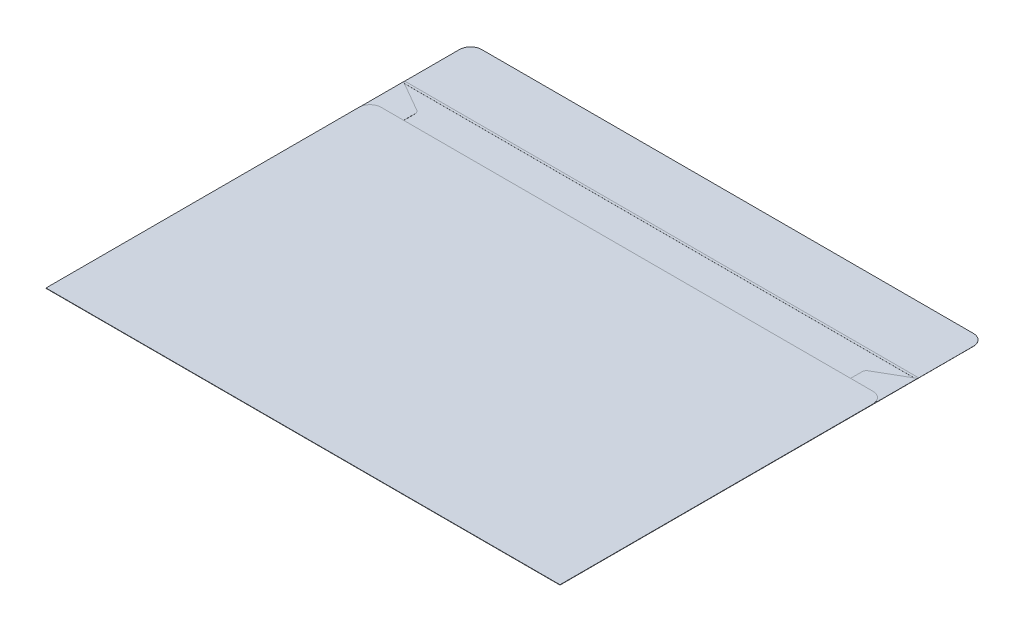
SolidWorks part; units mm, degrees
ref_plane "Front Plane" through (0, 0, 0) normal (0, 0, 1) x (1, 0, 0)
ref_plane "Top Plane" through (0, 0, 0) normal (0, 1, 0) x (1, 0, 0)
ref_plane "Right Plane" through (0, 0, 0) normal (1, 0, 0) x (0, 0, -1)
sketch "Sketch1" plane through (0, 0, 0) normal (0, 1, 0) x (1, 0, 0)
  line L2 (-115, 80) -> (-115, -80)
  line L3 (-115, -80) -> (115, -80)
  line L4 (115, 80) -> (115, -80)
  line L5 (0, -80) -> (0, 80) construction
  line L6 (-115, 0) -> (115, 0) construction
  line L8 (-115, 80) -> (-115, 105)
  line L9 (-110, 110) -> (110, 110)
  line L10 (115, 80) -> (115, 105)
  line L11 (0, 110) -> (0, 80) construction
  line L12 (-115, 92.5) -> (115, 92.5) construction
  arc A0 (110, 110) -> (115, 105) centre (110, 105) cw
  arc A1 (-110, 110) -> (-115, 105) centre (-110, 105) ccw
  point P0 (0, 0)
  point P11 (-115, 110)
  point P301 (0, 92.5)
  dimension "D4" = 5
  dimension "D1" = 160
  dimension "D2" = 230
  dimension "D3" = 30
extrude "Boss-Extrude1" add sketch "Sketch1" along normal blind 0.05
sketch "Sketch2" plane through (0, 0.05, 0) normal (0, 1, 0) x (1, 0, 0)
  line L0 (115, -80) -> (115, 105) construction
  line L1 (-115, -80) -> (115, -80)
  line L2 (-115, -80) -> (-115, 65)
  line L3 (-115, 65) -> (115, 65)
  line L4 (115, -80) -> (115, 65)
  line L5 (0, 65) -> (0, -80) construction
  line L6 (-115, -7.5) -> (115, -7.5) construction
  line L7 (-115, -80) -> (-115, 80)
  line L8 (-115, 105) -> (-115, -80) construction
  line L9 (-115, 80) -> (-100, 71.3397)
  line L10 (-100, 71.3397) -> (-100, -80)
  line L11 (-100, -80) -> (-115, -80)
  line L12 (100, -80) -> (115, -80)
  line L13 (100, 71.3397) -> (100, -80)
  line L14 (115, 80) -> (100, 71.3397)
  line L15 (115, -80) -> (115, 80)
  line L16 (-115, 80.5) -> (-115, 79.5) construction
  line L17 (-115, 80.5) -> (115, 80.5) construction
  line L18 (-115, 79.5) -> (115, 79.5) construction
  line L19 (115, 80.5) -> (115, 79.5) construction
  line L20 (-115, 80.5) -> (115, 79.5) construction
  line L21 (-115, 79.5) -> (115, 80.5) construction
  point P14 (0, 0)
  point P15 (0, 80)
  point P16 (0, 0)
  point P484 (0, -7.5)
  line M14 (115, -80) -> (115, 105)
  line M18 (-115, 105) -> (-115, -80)
  line M19 (-115, -80) -> (115, -80)
  dimension "D1" = 145
  dimension "D2" = 15
  dimension "D3" = 60
  dimension "D4" = 160
  dimension "D5" = 230
  dimension "D6" = 1
  dimension "D7" = 15
extrude "Boss-Extrude2" add sketch "Sketch2" along normal blind 0.1 contours L13 L3 L10 L1 | L10 L3 M18 M19 | L3 L13 M19 M14 region at (-107.5, 0.05, 7.5) region at (0, 0.05, 7.5) region at (107.5, 0.05, 7.5)
extrude "Boss-Extrude3" add sketch "Sketch2<3>" along normal blind 0.05 contours L18 L7 L3 L10 L9 | L18 L14 L13 L3 M14 region at (-108.5146, 0.05, -70.6278) region at (108.5146, 0.05, -70.6278)
sketch "Sketch2<3>" plane through (0, 0.05, 0) normal (0, 1, 0) x (1, 0, 0) same geometry as "Sketch2"
sketch "Sketch3" plane through (0, 0.05, 0) normal (0, 1, 0) x (1, 0, 0)
  line L0 (-115, 80) -> (115, 80) construction
  line L2 (-115, 80.5) -> (115, 80.5)
  line L3 (-115, 80.5) -> (-115, 79.5)
  line L4 (-115, 79.5) -> (115, 79.5)
  line L5 (115, 80.5) -> (115, 79.5)
  line L6 (0, 79.5) -> (0, 80.5) construction
  line L7 (-115, 80) -> (115, 80) construction
  point P4 (0, 80)
  dimension "D1" = 1
extrude "Boss-Extrude7" add sketch "Sketch3" along normal blind 0.03 and the other way blind 0.08
fillet "Fillet1" radius 5 2 edges at (115, 0.125, -65) (-115, 0.125, -65)
fillet "Fillet2" radius 2 2 edges at (100, 0.075, -71.3397) (-100, 0.075, -71.3397)
